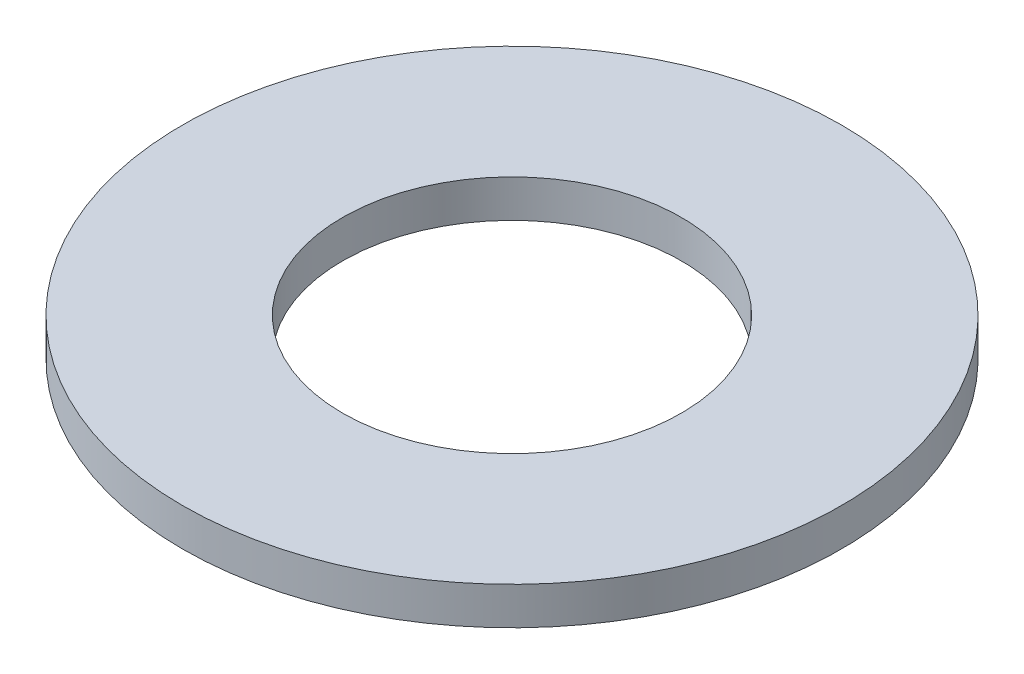
SolidWorks part; units mm, degrees
ref_plane "Front Plane" through (0, 0, 0) normal (0, 0, 1) x (1, 0, 0)
ref_plane "Top Plane" through (0, 0, 0) normal (0, 1, 0) x (1, 0, 0)
ref_plane "Right Plane" through (0, 0, 0) normal (1, 0, 0) x (0, 0, -1)
sketch "Sketch1" plane through (0, 0, 0) normal (0, 1, 0) x (1, 0, 0)
  circle A0 centre (0, 0) radius 87.5
  dimension "FLANGE_OD" = 175
extrude "Boss-Extrude1" add sketch "Sketch1" along normal blind 10
sketch "Sketch2" plane through (0, 0, 0) normal (0, 1, 0) x (1, 0, 0)
  circle A0 centre (0, 0) radius 45
  dimension "BORE_D" = 90
extrude "Cut-Extrude1" cut sketch "Sketch2" along normal through all
sketch "Sketch3" plane through (0, 10, 0) normal (0, 1, 0) x (1, 0, 0)
  circle A0 centre (0, 0) radius 35.9794 construction
  circle A1 centre (-35.9794, 0) radius 7.5636
  dimension "BOLT_D" = 15.1272
  dimension "BOLT_PCD" = 71.9588
extrude "Cut-Extrude2" cut sketch "Sketch3" against normal blind 8.4421 rebuild error yes
pattern_circular "CirPattern1" count 5 over 360 rebuild error yes
